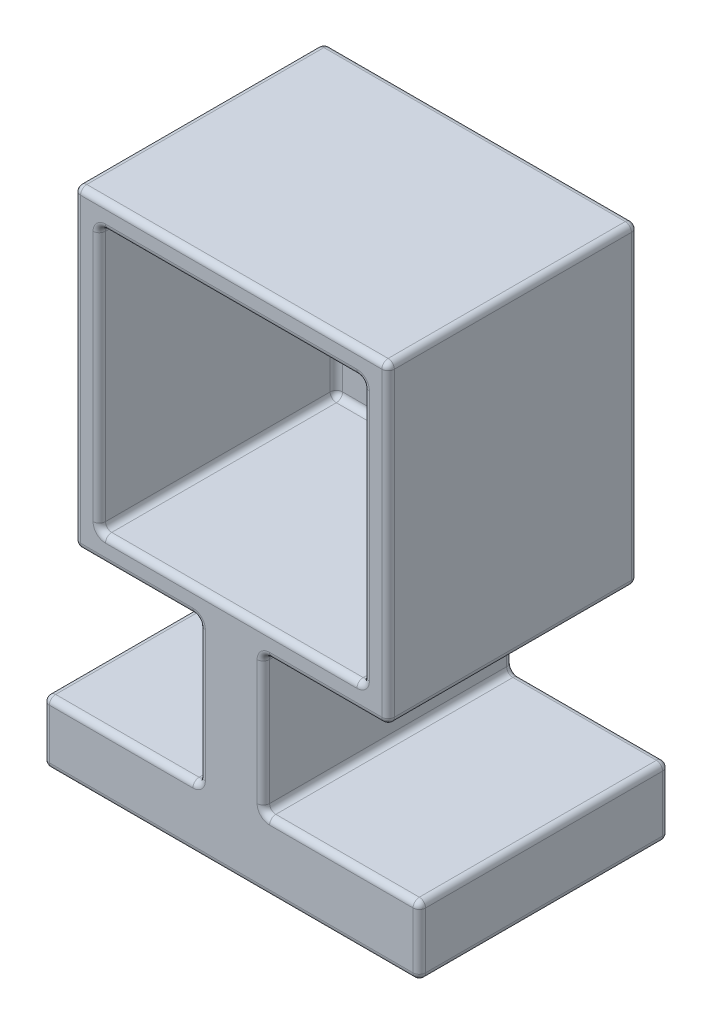
SolidWorks part; units mm, degrees
note: The reader was unsure of these and kept them because the rebuilt part matched: shared geometry of "Sketch1<5>", "Sketch1<6>".
ref_plane "Front Plane" through (0, 0, 0) normal (0, 0, 1) x (1, 0, 0)
ref_plane "Top Plane" through (0, 0, 0) normal (0, 1, 0) x (1, 0, 0)
ref_plane "Right Plane" through (0, 0, 0) normal (1, 0, 0) x (0, 0, -1)
sketch "Sketch1" plane through (0, 0, 0) normal (0, 0, 1) x (1, 0, 0)
  line L0 (0, 36.65) -> (5.65, 42.3)
  line L1 (0, 0) -> (42.3, 0)
  line L2 (0, 0) -> (0, 42.3)
  line L3 (0, 42.3) -> (42.3, 42.3)
  line L4 (42.3, 0) -> (42.3, 42.3)
  line L5 (36.65, 42.3) -> (42.3, 36.65)
  line L6 (36.65, 0) -> (42.3, 5.65)
  line L7 (5.65, 0) -> (0, 5.65)
  line L8 (-4, 46.3) -> (46.3, 46.3)
  line L9 (-4, 46.3) -> (-4, -4)
  line L10 (-4, -4) -> (46.3, -4)
  line L11 (46.3, 46.3) -> (46.3, -4)
  line L12 (16, -26.9913) -> (-9, -26.9913)
  line L13 (16, -4) -> (26.3, -4)
  line L14 (16, -4) -> (16, -26.9913)
  line L16 (26.3, -4) -> (26.3, -25.9913)
  line L17 (-9, -26.9913) -> (-9, -36.9913)
  line L18 (-9, -36.9913) -> (51.3, -36.9913)
  line L19 (51.3, -36.9913) -> (51.3, -25.9913)
  line L20 (51.3, -25.9913) -> (26.3, -25.9913)
  line L21 (21.15, 42.3) -> (21.15, 0) construction
  circle A0 centre (21.15, 21.15) radius 11
  dimension "D19" = 22
  dimension "D1" = 42.3
  dimension "D2" = 31
  dimension "D3" = 31
  dimension "D4" = 31
  dimension "D5" = 31
  dimension "D6" = 5.65
  dimension "D7" = 5.65
  dimension "D8" = 5.65
  dimension "D9" = 5.65
  dimension "D10" = 4
  dimension "D11" = 4
  dimension "D12" = 4
  dimension "D13" = 4
  dimension "D14" = 20
  dimension "D15" = 20
  dimension "D16" = 25
  dimension "D17" = 25
  dimension "D18" = 10
extrude "Boss-Extrude2" add sketch "Sketch1" along normal blind 2 contours L3 L21 A0 L1 L6 L4 L5 | L21 L3 L0 L2 L7 L1 A0
extrude "Boss-Extrude3" add sketch "Sketch1<5>" along normal blind 40 contours L11 L8 L9 L10 L4 L1 L2 L3 | L3 L2 L0 | L3 L5 L4 | L6 L1 L4 | L1 L7 L2 | L14 L12 L17 L18 L19 L20 L16 L13
sketch "Sketch1<5>" plane through (0, 0, 0) normal (0, 0, 1) x (1, 0, 0) same geometry as "Sketch1"
extrude "Cut-Extrude2" cut sketch "Sketch1<6>" against normal through all and the other way up to surface (2 mm away) contours A0 other way up to face at (21.15, 21.15, 2)
sketch "Sketch1<6>" plane through (0, 0, 0) normal (0, 0, 1) x (1, 0, 0) same geometry as "Sketch1"
fillet "Fillet1" radius 1 47 edges at (32.15, 21.15, 0) (21.15, 42.3, 2) (0, 21.15, 2) (21.15, 0, 2) (42.3, 21.15, 2) (21.15, 46.3, 40) (46.3, 46.3, 20) (0, 0, 21) (42.3, 0, 21) (21.15, 0, 40) (42.3, 42.3, 21) (42.3, 21.15, 40) (0, 42.3, 21) (-4, 21.15, 0) (-4, 46.3, 20) (46.3, 21.15, 40) (46.3, -4, 20) (46.3, 21.15, 0) (26.3, -14.9957, 0) (21.15, 46.3, 0) (0, 21.15, 40) (21.15, 42.3, 40) (-4, 21.15, 40) (6, -4, 40) (16, -15.4957, 40) (-9, -31.9913, 40) (21.15, -36.9913, 40) (51.3, -31.4913, 40) (38.8, -25.9913, 40) (36.3, -4, 40) (26.3, -4, 20) (36.3, -4, 0) (-4, -4, 20) (6, -4, 0) (51.3, -31.4913, 0) (51.3, -36.9913, 20) (21.15, -36.9913, 0) (-9, -36.9913, 20) (-9, -31.9913, 0) (-9, -26.9913, 20) (16, -26.9913, 20) (38.8, -25.9913, 0) (51.3, -25.9913, 20) (26.3, -14.9957, 40) (26.3, -25.9913, 20) (16, -15.4957, 0) (16, -4, 20)
